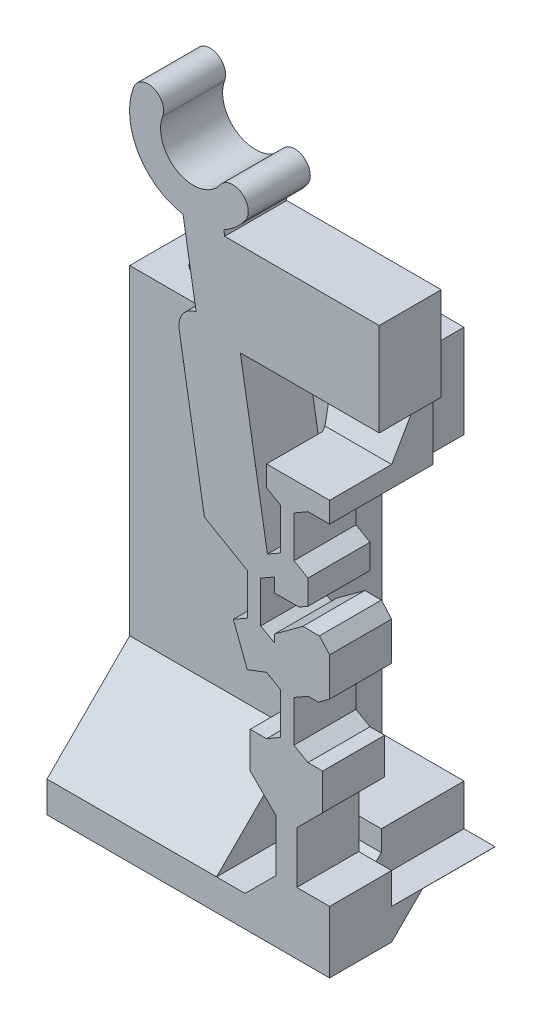
SolidWorks part; units mm, degrees
material "Nylon 6/12"
ref_plane "Front Plane" through (0, 0, 0) normal (0, 0, 1) x (1, 0, 0)
ref_plane "Top Plane" through (0, 0, 0) normal (0, 1, 0) x (1, 0, 0)
ref_plane "Right Plane" through (0, 0, 0) normal (1, 0, 0) x (0, 0, -1)
sketch "Sketch-SkeletonConfigUp" plane through (0, 0, 0) normal (0, 0, 1) x (1, 0, 0)
  line L0 (0, 0) -> (0, -50000) construction
  line L1 (0, 0) -> (4.5811, 6.2164) construction
  line L2 (9.8143, 13.3177) -> (4.5811, 13.945) construction
  line L3 (4.5811, 13.945) -> (2.9713, 10.4094) construction
  line L4 (2.9713, 10.4094) -> (4.5811, 6.2164) construction
  line L5 (4.5811, 13.945) -> (6.2429, 19.1409) construction
  line L6 (2.9713, 10.4094) -> (0.0405, 27.8193) construction
  line L7 (4.5811, 6.2164) -> (9.8143, 13.3177) construction
  line L8 (-587.3593, -797.0242) -> (9.8143, 13.3177) construction
  dimension "D2" = 7.7221
  dimension "D3" = 8.8212
  dimension "D4" = 5.2707
  dimension "D5" = 119.553
  dimension "D6" = 3.8848
  dimension "D7" = 5.4552
  dimension "D8" = 17.6549
  dimension "D9" = 4.4914
  dimension "D10" = 6.745
  dimension "D11" = 145.964
  dimension "D12" = 143.612
sketch "Sketch-SkeletonConfigDown" plane through (0, 0, 0) normal (0, 0, 1) x (1, 0, 0)
  line L0 (0, 0) -> (0, -50000) construction
  line L1 (0, 0) -> (4.5811, 6.2164) construction
  line L2 (9.8143, 13.3177) -> (4.5811, 13.945) construction
  line L3 (4.5811, 13.945) -> (6.1909, 10.4094) construction
  line L4 (6.1909, 10.4094) -> (4.5811, 6.2164) construction
  line L5 (4.5811, 13.945) -> (1.753, 18.6098) construction
  line L6 (6.1909, 10.4094) -> (-8.8652, 19.6294) construction
  line L7 (4.5811, 6.2164) -> (9.8143, 13.3177) construction
  line L8 (-589.9357, -800.5203) -> (9.8143, 13.3177) construction
  dimension "D2" = 7.7221
  dimension "D3" = 8.8212
  dimension "D4" = 5.2707
  dimension "D5" = 119.553
  dimension "D6" = 3.8848
  dimension "D7" = 5.4552
  dimension "D8" = 17.6549
  dimension "D9" = 4.4914
  dimension "D10" = 6.745
  dimension "D11" = 145.964
  dimension "D1" = 143.612
ref_plane "Plane-Cam Base" through (9.128, 0, 0) normal (1, 0, 0) x (0, 0, -1)
ref_plane "Plane-Down-to-Up Derailleur Clearance" through (6.628, 0, 0) normal (1, 0, 0) x (0, 0, -1)
ref_plane "Plane-Cam Cavity Roof" through (5.128, 0, 0) normal (1, 0, 0) x (0, 0, -1)
sketch "Sketch-SwitchBossUp" plane through (0, 0, 0) normal (0, 0, 1) x (1, 0, 0)
  line L0 (3.5811, 11.4759) -> (3.5811, 12.945) construction
  line L5 (5.5811, 12.5549) -> (5.5811, 11.3705)
  line L7 (1.5115, 25.1048) -> (1.5536, 24.8548)
  line L8 (-0.4607, 24.7728) -> (1.6966, 11.9577) construction
  line L9 (2.9713, 10.4094) -> (0.0405, 27.8193) construction
  line L11 (0.1364, 21.2256) -> (2.1086, 21.5576) construction
  line L15 (6.628, -23.7286) -> (6.628, 23.7286) construction
  line L16 (2.9713, 10.4094) -> (4.5811, 6.2164) construction
  line L17 (3.5811, 12.945) -> (3.5811, 14.945) construction
  line L18 (5.5811, 12.945) -> (5.5811, 14.945) construction
  line L19 (4.2561, 13.945) -> (4.9061, 13.945) construction
  line L20 (3.5811, 14.945) -> (5.5811, 14.945) construction
  line L21 (3.5811, 12.945) -> (5.5811, 12.945) construction
  line L22 (4.5811, 12.945) -> (4.5811, 14.945) construction
  line L23 (4.5811, 6.2164) -> (8.5404, 7.1023) construction
  line L24 (1.9713, 9.4094) -> (1.9713, 11.4094) construction
  line L25 (3.9713, 9.4094) -> (3.9713, 11.4094) construction
  line L26 (3.9713, 9.4094) -> (1.9713, 9.4094) construction
  line L27 (1.9713, 11.4094) -> (3.9713, 11.4094) construction
  line L28 (3.5811, 7.2164) -> (5.5811, 7.2164) construction
  line L29 (3.5811, 7.2164) -> (3.5811, 5.2164) construction
  line L30 (5.5811, 7.2164) -> (5.5811, 5.2164) construction
  line L31 (3.5811, 5.2164) -> (5.5811, 5.2164) construction
  line L32 (4.9061, 6.2164) -> (4.2561, 6.2164) construction
  line L40 (3.2963, 10.4094) -> (2.6463, 10.4094) construction
  line L66 (0.0405, 27.8193) -> (0.0405, 50027.8193) construction
  line L75 (4.5811, 3.3049) -> (4.5405, -0.6733) construction
  line L76 (5.5811, 11.3705) -> (5.5811, 12.5549) construction
  line L81 (9.1185, 1033.2334) -> (9.1185, 20.05) construction
  line L85 (6.9307, 9.5241) -> (9.1185, 7.0942) construction
  line L88 (5.7256, 16.335) -> (6.628, 16.335)
  line L92 (3.7762, 8.3129) -> (6.9307, 9.5241) construction
  line L101 (4.5811, 6.2164) -> (6.9307, 9.5241) construction
  line L103 (0.0405, 27.8193) -> (1.9448, 26.4638) construction
  line L104 (6.9307, 9.5241) -> (9.1185, 7.0942) construction
  line L107 (1.9713, 9.4094) -> (1.9713, 9.0197) construction
  line L109 (0.0405, 27.8193) -> (-2.1498, 28.6358) construction
  line L111 (6.628, 9.8603) -> (6.628, 8.0076)
  line L112 (6.628, 9.8603) -> (6.9307, 9.5241) construction
  line L114 (7.3693, 7.7363) -> (7.3563, 7.7363) construction
  line L121 (5.0405, -1.6882) -> (5.0405, -0.6733) construction
  line L122 (9.028, 22.3548) -> (9.028, 20.3548)
  line L127 (5.5811, 15.3347) -> (5.5811, 14.945) construction
  line L133 (2.9713, 10.4094) -> (6.1909, 10.4094) construction
  line L134 (4.5811, 10.4094) -> (4.5811, 13.945) construction
  line L135 (4.5811, 10.4094) -> (4.5811, 6.2164) construction
  line L137 (3.9713, 9.4094) -> (5.5811, 7.2164) construction
  line L139 (5.3335, 10.4094) -> (3.9713, 9.4094)
  line L142 (2.5405, -2.1733) -> (2.5405, -3.6733)
  line L143 (9.1185, 20.05) -> (9.1185, 18.3248) construction
  line L145 (9.1185, 16.5986) -> (9.1185, -49992.4252) construction
  line L147 (5.5811, 11.3705) -> (5.5811, 12.5549) construction
  line L150 (2.5405, -3.6733) -> (6.628, -3.6733)
  line L151 (4.0405, 1.8267) -> (5.0405, 1.8267) construction
  line L152 (4.2555, 14.945) -> (4.2555, 12.945)
  line L153 (4.9055, 14.945) -> (4.9055, 12.945)
  line L157 (3.5811, 16.335) -> (3.5811, 15.335)
  line L162 (3.2963, 11.4094) -> (3.2963, 9.4094)
  line L164 (2.6463, 11.4094) -> (2.6463, 9.4094)
  line L169 (4.2561, 7.2164) -> (4.2561, 5.2164)
  line L170 (4.9061, 5.2164) -> (4.9061, 7.2164)
  line L175 (4.2561, 7.2164) -> (3.5811, 7.6061)
  line L176 (4.9061, 7.2164) -> (5.5811, 7.6061)
  line L177 (5.5811, 7.2164) -> (5.5811, 7.6061) construction
  line L179 (4.2561, 5.2164) -> (3.5811, 4.8267)
  line L180 (3.5811, 5.2164) -> (3.5811, 4.8267) construction
  line L181 (3.5811, 4.8267) -> (2.7905, 4.8267)
  line L183 (4.9061, 5.2164) -> (5.5811, 4.8267)
  line L184 (5.5811, 5.2164) -> (5.5811, 4.8267) construction
  line L186 (9.128, -23.7286) -> (9.128, 23.7286) construction
  line L187 (2.6463, 9.4094) -> (1.9713, 9.0197)
  line L188 (3.2963, 9.4094) -> (3.9713, 9.0197)
  line L189 (3.2963, 11.4094) -> (3.9713, 11.7991)
  line L190 (2.6463, 11.4094) -> (1.6966, 11.9577)
  line L191 (3.9713, 11.4094) -> (3.9713, 11.7991) construction
  line L192 (3.9713, 11.7991) -> (3.9713, 11.1241)
  line L193 (4.9055, 12.945) -> (5.5811, 12.5549)
  line L194 (4.2555, 12.945) -> (3.6202, 12.5782)
  line L195 (3.9713, 11.1241) -> (5.1543, 11.1241)
  line L196 (3.9713, 9.4094) -> (3.9713, 9.0197)
  line L197 (3.5811, 7.2164) -> (3.5811, 7.6061) construction
  line L199 (3.5811, 7.6061) -> (2.6469, 7.2496)
  line L201 (2.7905, 3.0767) -> (2.7905, 4.8267)
  line L202 (2.7905, 3.0767) -> (6.2905, 3.0767) construction
  line L207 (9.1185, 18.3248) -> (9.1185, 16.5986) construction
  line L208 (6.628, -3.6733) -> (6.628, -0.6733)
  line L209 (9.1185, 20.05) -> (9.1185, 16.5986) construction
  line L211 (5.0405, -0.6733) -> (5.0405, 1.8267)
  line L212 (4.0405, -0.6733) -> (4.0405, 1.8267)
  line L214 (4.2555, 14.945) -> (3.5798, 15.335)
  line L215 (3.5798, 15.335) -> (3.5811, 15.335)
  line L216 (4.9055, 14.945) -> (5.5811, 15.335)
  line L217 (5.5811, 12.945) -> (5.5811, 12.5549) construction
  line L218 (4.9055, 14.945) -> (4.9055, 15.335) construction
  line L219 (5.5811, 15.335) -> (3.5798, 15.335) construction
  line L221 (9.028, 22.3548) -> (9.028, 24.8548)
  line L224 (3.5811, 16.335) -> (5.7256, 16.335)
  line L232 (6.628, 15.335) -> (6.628, 16.335)
  line L236 (1.5536, 24.8548) -> (9.028, 24.8548)
  line L250 (9.028, 20.3548) -> (2.3111, 20.3548)
  line L254 (5.0405, -0.6733) -> (4.0405, -0.6733) construction
  line L255 (4.0405, -0.6733) -> (3.0345, -0.6733) construction
  line L256 (4.5811, 6.2164) -> (4.5811, 3.3049) construction
  line L259 (5.0405, -0.6733) -> (6.628, -0.6733)
  line L261 (1.6966, 11.9577) -> (0.5733, 12.6062)
  line L262 (0.5733, 12.6062) -> (-0.6452, 19.8444)
  line L263 (4.0405, 1.8267) -> (2.7905, 3.0767)
  line L266 (5.0405, 1.8267) -> (6.2905, 3.0767)
  line L270 (2.5405, -2.1733) -> (4.0405, -0.6733)
  line L279 (0.175, 20.9965) -> (-0.4607, 24.7728)
  line L283 (2.3111, 20.3548) -> (3.6202, 12.5782)
  line L367 (5.5811, 4.8267) -> (6.2905, 4.8267)
  line L368 (6.2905, 4.8267) -> (6.2905, 3.0767)
  line L471 (2.6469, 7.2496) -> (1.9713, 9.0197)
  line L472 (6.1335, 10.4094) -> (6.628, 9.8603)
  line L473 (5.3335, 10.4094) -> (6.1335, 10.4094)
  line L474 (5.5811, 7.6061) -> (6.0811, 7.6061)
  line L475 (6.0811, 7.6061) -> (6.628, 8.0076)
  line L477 (5.1543, 11.1241) -> (5.5811, 11.3705)
  line L478 (5.5811, 15.335) -> (6.628, 15.335)
  line L479 (5.5811, 14.945) -> (6.9307, 14.945) construction
  arc A0 (1.5115, 25.1048) -> (2.5558, 26.0289) centre (0.0405, 27.8193) ccw
  arc A1 (-1.5413, 25.1678) -> (-2.8525, 28.8978) centre (0.0405, 27.8193) cw
  arc A2 (-2.8525, 28.8978) -> (-1.447, 28.3738) centre (-2.1498, 28.6358) cw
  arc A3 (2.5558, 26.0289) -> (1.3338, 26.8987) centre (1.9448, 26.4638) ccw
  arc A4 (-1.447, 28.3738) -> (1.3338, 26.8987) centre (0.0405, 27.8193) ccw
  arc A5 (3.5811, 12.945) -> (3.5811, 14.945) centre (3.1778, 13.945) ccw construction
  arc A6 (5.5811, 12.945) -> (5.5811, 14.945) centre (5.9843, 13.945) cw construction
  arc A7 (2.528, 9.9183) -> (1.9713, 11.4094) centre (1.568, 10.4094) ccw construction
  arc A8 (3.9713, 11.4094) -> (3.9713, 9.4094) centre (4.3745, 10.4094) ccw construction
  arc A9 (3.5811, 7.2164) -> (3.5811, 5.2164) centre (3.1779, 6.2164) cw construction
  arc A10 (5.5811, 7.2164) -> (5.5811, 5.2164) centre (5.9844, 6.2164) ccw construction
  circle A28 centre (0.0405, 27.8193) radius 2.3375 construction
  arc A29 (1.9713, 9.4094) -> (2.528, 9.9183) centre (1.568, 10.4094) ccw construction
  arc A38 (-0.6452, 19.8444) -> (0.175, 20.9965) centre (0.341, 20.0104) cw
  arc A39 (-1.5413, 25.1678) -> (-0.4607, 24.7728) centre (0.0405, 27.8193) ccw
  point P53 (4.5811, 13.945)
  point P63 (2.9713, 10.4094)
  point P93 (1.1225, 21.3916)
  dimension "D23" = 1.5875
  dimension "D24" = 0.75
  dimension "D2" = 2
  dimension "D5" = 2
  dimension "D16" = 42
  dimension "D27" = 120
  dimension "D28" = 120
  dimension "D29" = 120
  dimension "D30" = 120
  dimension "D31" = 120
  dimension "D32" = 120
  dimension "D33" = 120
  dimension "D34" = 120
  dimension "D21" = 1
  dimension "D38" = 2
  dimension "D42" = 45
  dimension "D43" = 120
  dimension "D15" = 0.25
  dimension "D6" = 0.65
  dimension "D12" = 1
  dimension "D19" = 0.65
  dimension "D20" = 1
  dimension "D18" = 1.5
  dimension "D36" = 3
  dimension "D37" = 2.5
  dimension "D44" = 5
  dimension "D73" = 2.5
  dimension "D10" = 45
  dimension "D74" = 3.5
  dimension "D75" = 3
  dimension "D76" = 1
  dimension "D8" = 42
  dimension "D39" = 0.8
  dimension "D40" = 0.5
  dimension "D41" = 0.675
  dimension "D77" = 1.183
  dimension "D25" = 120
  dimension "D26" = 120
  dimension "D78" = 120
  dimension "D35" = 120
extrude "Boss-Switch Body" add sketch "Sketch-SwitchBossUp" along normal blind 3
sketch "Sketch1" plane through (0, 0, 0) normal (0, 0, -1) x (-1, 0, 0)
  line L1 (-6.628, -3.6733) -> (-2.5405, -3.6733)
  line L2 (-6.628, -3.6733) -> (-6.628, -2.1733)
  line L4 (-2.5405, -3.6733) -> (-2.5405, -2.1733)
  line L5 (-3.5811, 18.835) -> (-6.628, 18.835)
  line L10 (-6.628, 18.835) -> (-6.628, 15.335)
  line L12 (-6.628, 15.335) -> (-3.5811, 15.335)
  line L13 (-6.628, -2.1733) -> (-2.5405, -2.1733)
  line L14 (-3.5811, 15.335) -> (-3.5811, 18.835)
  line L22 (-2.5405, -3.6733) -> (-6.628, -3.6733) construction
  line L25 (-6.628, -3.6733) -> (-6.628, -0.6733) construction
  dimension "D1" = 3.5
extrude "Boss-Flange Width" add sketch "Sketch1" along normal blind 5
ref_plane "Plane-Sta2Sit Groove" through (0.0405, 0, 0) normal (1, 0, 0) x (0, 0, -1)
ref_plane "Plane-Cam Outer Surface" through (-12.0395, 0, 0) normal (1, 0, 0) x (0, 0, -1)
ref_plane "Plane-FlangeTop" through (-7.0395, 0, 0) normal (1, 0, 0) x (0, 0, -1)
sketch "Sketch2" plane through (-7.0395, 0, 0) normal (1, 0, 0) x (0, 0, -1)
  line L0 (5, 15.335) -> (0, 15.335) construction
  line L1 (5, 17.335) -> (1, 17.335)
  line L2 (5, 17.335) -> (5, 15.335)
  line L3 (5, 15.335) -> (1, 15.335)
  line L4 (1, 17.335) -> (1, 15.335)
  line L5 (-3, -3.6733) -> (-3, -0.6733) construction
  line L12 (5, -2.1733) -> (5, -3.6733)
  line L13 (5, -3.6733) -> (-3, -3.6733)
  line L14 (-3, -2.1733) -> (-3, -3.6733)
  line L15 (0, 10.4094) -> (0, 27.8193) construction
  line L16 (1, 15.335) -> (1, -0.6733) construction
  line L22 (5, -2.1733) -> (0, -2.1733) construction
  line L23 (5, -2.1733) -> (-3, -2.1733)
  dimension "D1" = 1
  dimension "D2" = 2
  dimension "D3" = 16.0083
extrude "Boss-Flange Height" add sketch "Sketch2" along normal up to surface (10.6206 mm away) up to face at (3.5811, 16.6208, -0.5714)
sketch "Sketch10" plane through (0, 15.335, 0) normal (0, 1, 0) x (1, 0, 0)
  line L0 (9.128, -23.7286) -> (9.128, 23.7286) construction
  line L1 (6.628, 5) -> (5.128, 5)
  line L2 (6.628, 5) -> (6.628, 2)
  line L3 (6.628, 2) -> (5.128, 2)
  line L5 (4.628, 7) -> (4.628, 0.64) construction
  line L6 (3.5811, 1) -> (-7.0395, 1) construction
  line L8 (5.128, 5) -> (5.128, 2)
  dimension "D1" = 1
  dimension "D2" = 0.5
  dimension "D3" = 4.5
extrude "Cut-Up-To-Down Derailleur Clearance" cut sketch "Sketch10" along normal up to next
sketch "Sketch17" plane through (0, 15.335, 0) normal (0, -1, 0) x (1, 0, 0)
  line L0 (5.128, -5) -> (-7.0395, -5)
  line L1 (5.128, -5) -> (-7.0395, -5) construction
  line L2 (-7.0395, -5) -> (-7.0395, -1)
  line L3 (-7.0395, -1) -> (5.128, -1)
  line L4 (5.128, -1) -> (5.128, -5)
  line L5 (-7.0395, -1) -> (-7.0395, -5) construction
  line L6 (5.128, -5) -> (5.128, -2) construction
extrude "Boss-Flange Support" add sketch "Sketch17" along normal up to surface (17.5083 mm away) up to face at (0.7096, -2.1733, -0.6667)
sketch "Sketch-HolePositions" plane through (0, -3.6733, 0) normal (0, -1, 0) x (1, 0, 0)
  line L0 (-7.0395, -3) -> (6.628, -3) construction
  line L1 (6.628, -5) -> (-7.0395, -5) construction
  line L2 (6.628, -5) -> (6.628, 3) construction
  line L4 (-7.0395, -22.2167) -> (-7.0395, 22.2167) construction
  point P6 (-5.0395, -3)
  point P7 (-0.5395, -3)
  dimension "D1" = 2
  dimension "D2" = 4.5
  dimension "D3" = 2
sketch "Sketch6" plane through (0, -3.6733, 0) normal (0, -1, 0) x (-1, 0, 0)
  point P0 (5.0395, 3)
  point P3 (0.5395, 3)
hole_wizard "Tap Drill for M2x0.4 Tap1" positions "Sketch6" profile "Sketch5" hole size "M2x0.4" standard "ANSI Metric" end condition through all
sketch "Sketch5" plane through (-5.0395, -3.6733, -3) normal (1, 0, 0) x (0, 0, -1)
  line L0 (0, 0) -> (0, 33.0591)
  line L1 (0, 33.0591) -> (0.8, 33.0591)
  line L2 (0.8, 33.0591) -> (0.8, 0)
  line L5 (0.8, 0) -> (0, 0)
  line L11 (0, -6.35) -> (0, 107.95) construction
  dimension "Thru Hole Dia." = 1.6
  dimension "Thru Hole Depth" = 33.0591
sketch "Sketch9" plane through (0, -3.6733, 0) normal (0, -1, 0) x (1, 0, 0)
  point P0 (-5.0395, -3)
  point P3 (-0.5395, -3)
hole_wizard "M2 Clearance Hole2" positions "Sketch9" profile "Sketch8" hole size "M2" standard "ANSI Metric"
sketch "Sketch8" plane through (-5.0395, -3.6733, -3) normal (1, 0, 0) x (0, 0, -1)
  line L0 (0, 0) -> (0, 15.721)
  line L1 (0, 15.721) -> (1.2, 15)
  line L2 (1.2, 15) -> (1.2, 0)
  line L5 (1.2, 0) -> (0, 0)
  line L10 (0, 15.721) -> (-1.2, 15) construction
  line L11 (0, -6.35) -> (0, 107.95) construction
  dimension "Hole Dia." = 2.4
  dimension "Hole Depth" = 15
  dimension "Drill Angle" = 118
sketch "Sketch-Measurements for Derailleur Ramps" [suppressed] plane through (0, 0, 0) normal (0, 0, 1) x (1, 0, 0)
  line L0 (3.184, 15.1695) -> (2.4687, 19.4188)
  line L1 (2.8264, 17.2941) -> (1.8402, 17.1281)
  line L2 (2.9713, 10.4094) -> (0.0405, 27.8193) construction
  line L3 (1.8402, 17.1281) -> (-1.3081, 15.0016)
  line L4 (6.1909, 10.4094) -> (-8.8652, 19.6294) construction
  line L5 (1.8402, 17.1281) -> (2.6012, 12.6077)
  line L6 (2.6012, 12.6077) -> (-1.3081, 15.0016)
  line L7 (0.2661, 16.0649) -> (0.2661, 17.1281)
  line L8 (0.2661, 17.1281) -> (1.8402, 17.1281)
  line L9 (6.1909, 10.4094) -> (2.9713, 10.4094)
  line L10 (5.386, 8.3129) -> (3.7762, 8.3129)
  line L11 (2.6116, 18.5698) -> (1.5115, 25.1048) construction
  line L12 (6.1909, 10.4094) -> (4.5811, 6.2164) construction
  line L13 (4.5811, 8.3129) -> (4.5811, 8.7912)
  line L14 (4.5811, 6.2164) -> (5.386, 8.3129)
  line L15 (2.9713, 10.4094) -> (4.5811, 6.2164) construction
  line L16 (3.7762, 8.3129) -> (4.5811, 6.2164)
  line L17 (5.386, 8.3129) -> (5.386, 8.7912)
  dimension "D1" = 1.5742
  dimension "D2" = 0.8049
ref_plane "Plane1" through (0, 7.1023, 0) normal (0, 1, 0) x (1, 0, 0)
ref_plane "Plane-Cantilever Cut" [suppressed] through (7.0848, 8.5204, -1.9058) normal (-0.6301, -0.7578, 0.1695) x (-0.7765, 0.6151, -0.1368)
sketch "Sketch14" [suppressed] plane through (7.0848, 8.5204, -1.9058) normal (-0.6301, -0.7578, 0.1695) x (-0.7765, 0.6151, -0.1368)
  line L0 (2.3023, -1.6911) -> (-0.3551, -1.6911)
  line L2 (2.3023, -4.3362) -> (2.3023, -1.6911)
  line L3 (-0.3551, -1.6911) -> (-0.3551, -4.4608)
  line L5 (-0.3551, -4.4608) -> (1.0087, -5.0843)
  line L6 (1.0087, -5.0843) -> (2.3023, -4.3362)
extrude "Cut-Down-to-Up Cantilever Slope" [suppressed] cut sketch "Sketch14" against normal up to next
ref_plane "Plane-Symmetry Plane" through (0, 0, 1.5) normal (0, 0, 1) x (1, 0, 0)
sketch "Sketch-Cable Center Point" plane through (0, 0, 1.5) normal (0, 0, 1) x (1, 0, 0)
  line L0 (0.0405, 27.8193) -> (0.1722, 27.0366)
  line L1 (2.9713, 10.4094) -> (0.0405, 27.8193) construction
  point P0 (0.0405, 27.8193)
  dimension "D1" = 0.7937
chamfer "Chamfer-Flange Support" distance 1.5 angle 45 1 edges at (3.5811, 17.335, -3)
chamfer "Chamfer-Flange Support 2" distance 1 angle 45 2 edges at (5.128, 17.085, -2) (5.128, 15.335, -1.5)
chamfer "Chamfer7" [suppressed] distance 1 angle 45
sketch "Sketch27" plane through (5.128, 0, 0) normal (1, 0, 0) x (0, 0, -1)
  line L0 (3, 18.835) -> (3, 14.335) construction
  line L1 (2, 18.835) -> (5, 18.835)
  line L2 (2, 18.835) -> (2, 15.335)
  line L3 (2, 15.335) -> (5, 15.335)
  line L4 (5, 18.835) -> (5, 15.335)
  line L5 (5, 18.835) -> (5, -2.1733) construction
  line L6 (2, 18.835) -> (3, 18.835) construction
  line L8 (5, 15.335) -> (3, 15.335) construction
  dimension "D1" = 1
extrude "Cut-Wide Derailleur Clearance" [suppressed] cut sketch "Sketch27" against normal blind 4 and the other way through all
chamfer "Chamfer9" [suppressed] distance 1.25 angle 45
sketch "Sketch28" plane through (0, 0, -1) normal (0, 0, 1) x (1, 0, 0)
  line L0 (3.5811, 18.835) -> (6.628, 18.835)
  line L1 (6.628, 18.835) -> (6.628, 16.335)
  line L2 (6.628, 16.335) -> (3.5811, 16.335)
  line L3 (3.5811, 16.335) -> (3.5811, 18.835)
extrude "Cut-Extrude1" cut sketch "Sketch28" along normal up to surface (1 mm away) up to face at (5.1045, 17.585, 0)
chamfer "Chamfer10" distance 1 angle 60 1 edges at (5.1045, 16.335, -1) first distance on face at (5.1045, 16.335, 1)
chamfer "Chamfer-Flange Support 3" distance 1 angle 45 1 edges at (-0.9558, -2.1733, -1)
sketch "Sketch31" plane through (-7.0395, 0, 0) normal (-1, 0, 0) x (0, 0, 1)
  line L0 (-5, -2.1807) -> (-5, -3.6733)
  line L1 (-5, -3.6733) -> (-5, 17.335) construction
  line L2 (-5, -3.6733) -> (0, -3.6733)
  line L3 (0, 200000) -> (0, -250000) construction
  line L4 (3, -3.6733) -> (-5, -3.6733) construction
  line L5 (0, -3.6733) -> (-1.4926, -2.1807)
  line L7 (-1.4926, -2.1807) -> (-5, -2.1807)
  line L8 (0, -2.1733) -> (-1, -1.1733) construction
  dimension "D1" = 30
extrude "Cut-Extrude2" cut sketch "Sketch31" against normal through all
chamfer "Chamfer12" distance 0.5 angle 60 1 edges at (4.8545, 15.335, -1) first distance on face at (5.4795, 15.335, 0)
sketch "Sketch23" plane through (0, 0, -1) normal (0, 0, 1) x (1, 0, 0)
  line L0 (8.5877, -0.1733) -> (1.1605, -0.1733)
  line L2 (1.1605, -0.1733) -> (1.1605, 14.335)
  line L3 (1.1605, 14.335) -> (8.5877, 14.335)
  line L4 (8.5877, 14.335) -> (8.5877, -0.1733)
  line L5 (0.6605, -2.1807) -> (0.6605, 11.3267) construction
  line L11 (2.5405, -2.1733) -> (-7.0395, -2.1733) construction
  point P4 (8.5877, 14.2145)
  dimension "D1" = 0.5
  dimension "D2" = 2
extrude "Cut-Gap for Printing" cut sketch "Sketch23" against normal through all
sketch "Sketch32" plane through (-7.0395, 0, 0) normal (-1, 0, 0) x (0, 0, 1)
  line L0 (3, -2.1733) -> (-1, 1.8267)
  line L1 (-1, 17.335) -> (-1, -1.1733) construction
  line L2 (-1, 1.8267) -> (-1, -2.0828)
  line L3 (-1, -2.0828) -> (0.4063, -3.3555)
  line L4 (0.4063, -3.3555) -> (3, -3.3555)
  line L5 (3, -2.1733) -> (3, -3.6733) construction
  line L6 (3, -3.3555) -> (3, -2.1733)
  line L7 (3, -2.1733) -> (0, -2.1733) construction
  dimension "D1" = 45
extrude "Boss-Extrude2" add sketch "Sketch32" against normal up to surface (8.2 mm away) up to face at (1.1605, 7.0809, -3)
chamfer "Chamfer11" distance 0.75 angle 60 1 edges at (3.5811, 16.2681, -1) first distance on face at (2.0593, 14.1447, -1)
equation "\"axle-diameter\"=2"
equation "\"switch-thickness\"=12"
equation "\"base-width\"=4.0"
equation "\"axle-bushing-radius\"=3"
equation "\"clearance\"= 0.25"
equation "\"arm-width\"=1.5"
equation "\"min-diameter\"=70"
equation "\"alpha\"=143.6120"
equation "\"gamma\"=119.5526"
equation "\"delta\"=145.9637"
equation "\"epsilon\"=6.7452"
equation "\"l_AB\"=8.8212"
equation "\"l_AC\"=4.4914"
equation "\"l_BD\"=5.2707"
equation "\"l_CD\"=3.8848"
equation "\"l_CE\"=17.6549"
equation "\"l_DF\"=5.4552"
equation "\"l_OA\"=7.7221"
equation "\"D2@Sketch-SkeletonConfigUp\" = \"l_OA\""
equation "\"D3@Sketch-SkeletonConfigUp\" = \"l_AB\""
equation "\"D4@Sketch-SkeletonConfigUp\" = \"l_BD\""
equation "\"D5@Sketch-SkeletonConfigUp\" = \"gamma\""
equation "\"D6@Sketch-SkeletonConfigUp\" = \"l_CD\""
equation "\"D7@Sketch-SkeletonConfigUp\" = \"l_DF\""
equation "\"D8@Sketch-SkeletonConfigUp\" = \"l_CE\""
equation "\"D9@Sketch-SkeletonConfigUp\" = \"l_AC\""
equation "\"D_groove\"=3.175"
equation "\"D7@Sketch-SkeletonConfigDown\" = \"l_DF\""
equation "\"D6@Sketch-SkeletonConfigDown\" = \"l_CD\""
equation "\"D2@Sketch-SkeletonConfigDown\" = \"l_OA\""
equation "\"D3@Sketch-SkeletonConfigDown\" = \"l_AB\""
equation "\"D9@Sketch-SkeletonConfigDown\" = \"l_AC\""
equation "\"D8@Sketch-SkeletonConfigDown\" = \"l_CE\""
equation "\"D5@Sketch-SkeletonConfigDown\" = \"gamma\""
equation "\"D4@Sketch-SkeletonConfigDown\" = \"l_BD\""
equation "\"D1@Sketch-SkeletonConfigDown\" = \"alpha\""
equation "\"hinge_length\"=1.5"
equation "\"hinge_depth\"=0.25"
equation "\"D10@Sketch-SkeletonConfigUp\"=\"epsilon\""
equation "\"D11@Sketch-SkeletonConfigUp\"=\"delta\""
equation "\"D12@Sketch-SkeletonConfigUp\"=\"alpha\""
equation "\"D11@Sketch-SkeletonConfigDown\"=\"delta\""
equation "\"D10@Sketch-SkeletonConfigDown\"=\"epsilon\""
equation "\"EE_dx\"=8.9056"
equation "\"EE_dy\"=8.1898"
equation "\"r_groove\"=\"D_groove\"/2"
equation "\"t_wall\"=25.4/16"
equation "\"width_lower\"=\"D_groove\"+\"t_wall\""
equation "\"cable_to_bottom\"=30.6257"
equation "\"switch_EE-up_base_dy\"=24"
equation "\"switch_EE-down_base_dy\"=16"
equation "\"D_axle\"=25.4/8"
equation "\"D_up_to_down\"=16"
equation "\"D_down_to_up\"=25"
equation "\"t_cam_base\"=7.5"
equation "\"D23@Sketch-SwitchBossUp\"=\"D_groove\"/2"
equation "\"D1@Sketch-Cable Center Point\"=\"D_groove\"/4"
